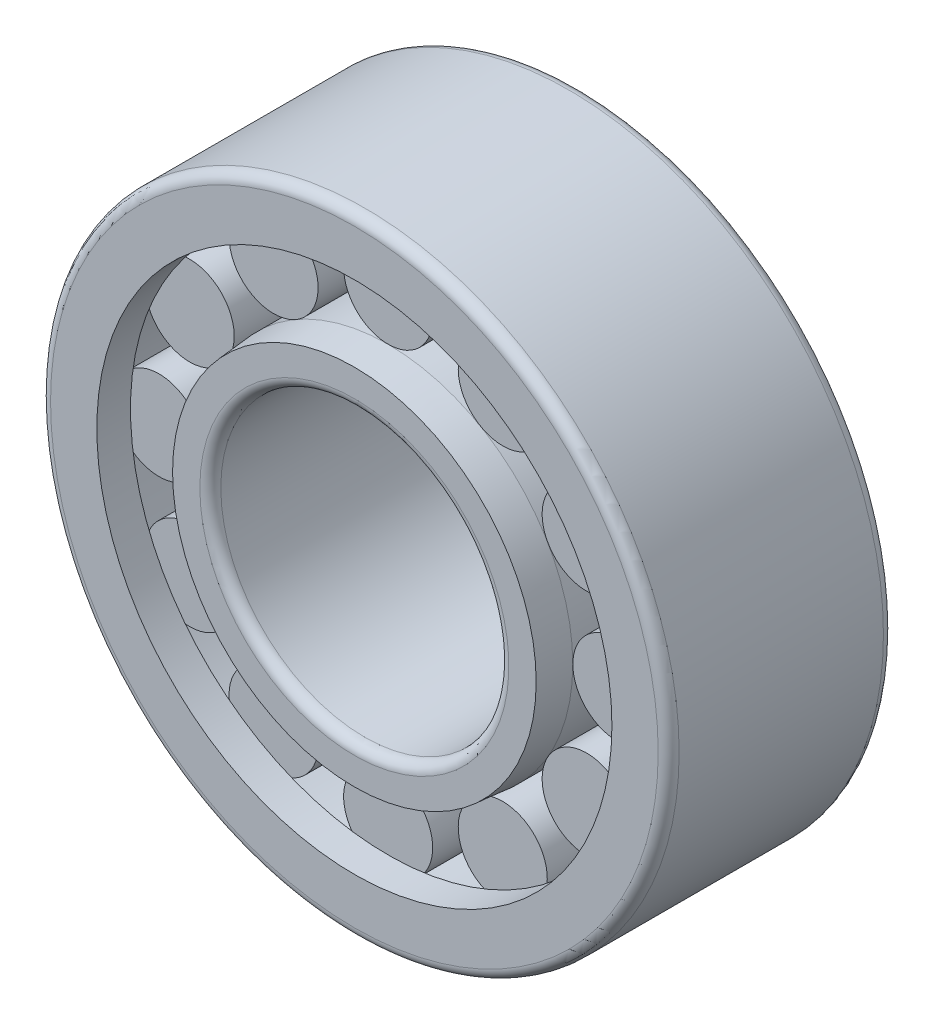
SolidWorks part; units mm, degrees
ref_plane "Front Plane" through (0, 0, 0) normal (0, 0, 1) x (1, 0, 0)
ref_plane "Top Plane" through (0, 0, 0) normal (0, 1, 0) x (1, 0, 0)
ref_plane "Right Plane" through (0, 0, 0) normal (1, 0, 0) x (0, 0, -1)
sketch "BaseSke" plane through (0, 0, 0) normal (1, 0, 0) x (0, 0, -1)
  line L0 (-47.2296, 0) -> (24.6132, 0) construction
  line L1 (-47.2296, 43.75) -> (24.6132, 43.75) construction
  line L2 (0, 129.5214) -> (0, -86.3012) construction
  line L3 (-15.05, 43.75) -> (-15.05, 52.25) construction
  line L4 (-21.5, 60) -> (21.5, 60) construction
  line L5 (-21.5, 27.5) -> (21.5, 27.5) construction
  line L6 (-15.05, 35.25) -> (15.05, 35.25)
  line L7 (-15.05, 35.25) -> (-15.05, 43.75)
  line L8 (-15.05, 43.75) -> (15.05, 43.75)
  line L9 (15.05, 35.25) -> (15.05, 43.75)
  line L10 (-15.05, 52.25) -> (15.05, 52.25) construction
  line L11 (15.05, 52.25) -> (15.05, 43.75) construction
  dimension "D2" = 30.1
  dimension "D1" = 87.5
revolve "Roller" add sketch "BaseSke" angle 360 about L8
sketch "OuterRaceSke" plane through (0, 0, 0) normal (1, 0, 0) x (0, 0, -1)
  line L0 (0, 0) -> (0, 87.5396) construction
  line L1 (-21.5, 60) -> (21.5, 60)
  line L2 (-21.5, 60) -> (-21.5, 49.1667)
  line L3 (-21.5, 49.1667) -> (-15.075, 49.1667)
  line L4 (21.5, 60) -> (21.5, 49.1667)
  line L5 (-50.3916, 0) -> (55.2197, 0) construction
  line L6 (-15.05, 52.25) -> (15.05, 52.25) construction
  line L7 (15.075, 49.1667) -> (21.5, 49.1667)
  line L9 (-15.075, 49.1667) -> (-15.075, 52.23)
  line L10 (-15.075, 52.23) -> (15.075, 52.23)
  line L11 (15.075, 49.1667) -> (15.075, 52.23)
  dimension "D2" = 98.3333
  dimension "D1" = 30.15
  dimension "D3" = 0.02
revolve "OuterRace" add sketch "OuterRaceSke" angle 360 about L5
sketch "InnerRaceSke" plane through (0, 0, 0) normal (1, 0, 0) x (0, 0, -1)
  line L0 (-70.8626, 0) -> (113.5527, 0) construction
  line L1 (0, 58.441) -> (0, -70.8113) construction
  line L2 (-21.5, 27.5) -> (21.5, 27.5)
  line L3 (-21.5, 27.5) -> (-21.5, 38.3333)
  line L4 (-15.075, 38.3333) -> (-15.075, 35.27)
  line L5 (-15.075, 38.3333) -> (-21.5, 38.3333)
  line L6 (0, 129.5214) -> (0, -86.3012) construction
  line L7 (-15.075, 35.27) -> (15.075, 35.27)
  line L9 (21.5, 27.5) -> (21.5, 38.3333)
  line L10 (15.075, 38.3333) -> (21.5, 38.3333)
  line L11 (15.075, 35.27) -> (15.075, 38.3333)
  line L13 (-15.05, 35.25) -> (15.05, 35.25) construction
  point P17 (0, 27.5)
  dimension "D1" = 30.15
  dimension "D2" = 0.02
  dimension "D3" = 76.6667
revolve "InnerRace" add sketch "InnerRaceSke" angle 360 about L0
fillet "Fillet1" radius 2 4 edges at (27.5, 0, 21.5) (60, 0, -21.5) (60, 0, 21.5) (27.5, 0, -21.5)
sketch "CutGrooveSke" plane through (0, 0, 0) normal (1, 0, 0) x (0, 0, -1)
  line L0 (-51.8407, 0) -> (83.8302, 0) construction
  line L1 (-10.75, -78.8) -> (-12.9, -78.8)
  line L2 (-10.75, -78.8) -> (-10.75, -58.8)
  line L3 (-10.75, -58.8) -> (-12.9, -58.8)
  line L4 (-12.9, -78.8) -> (-12.9, -58.8)
  dimension "D1" = 58.8
  dimension "D3" = 2.15
  dimension "D4" = 20
  dimension "D2" = 10.75
revolve "CutGroove" [suppressed] cut sketch "CutGrooveSke" angle 360 about L0
sketch "TaperSke" plane through (0, 0, 0) normal (1, 0, 0) x (0, 0, -1)
  line L0 (-21.5, 27.5) -> (21.5, 27.5)
  line L1 (21.5, 27.5) -> (21.5, 31.0833)
  line L2 (21.5, 31.0833) -> (-21.5, 27.5)
  line L7 (-41.2502, 0) -> (40.8606, 0) construction
revolve "Taper" [suppressed] cut sketch "TaperSke" angle 360 about L7
fillet "Fillet2" [suppressed] radius 2
sketch "NFSke" plane through (0, 0, 0) normal (1, 0, 0) x (0, 0, -1)
  line L0 (-54.6114, 0) -> (63.7655, 0) construction
  line L1 (21.5, 52.7921) -> (15.075, 52.23)
  line L2 (15.075, 52.23) -> (15.075, 49.1667)
  line L3 (15.075, 49.1667) -> (21.5, 49.1667)
  line L4 (21.5, 49.1667) -> (21.5, 52.7921)
  dimension "D1" = 5
revolve "NF" [suppressed] cut sketch "NFSke" angle 360 about L0
mirror "N" [suppressed] about plane through (0, 0, 0) normal (0, 0, 1)
sketch "NJSke" plane through (0, 0, 0) normal (1, 0, 0) x (0, 0, -1)
  line L0 (-35.6078, 0) -> (44.429, 0) construction
  line L1 (21.5, 38.3333) -> (15.075, 38.3333)
  line L2 (15.075, 38.3333) -> (15.075, 35.27)
  line L3 (15.075, 35.27) -> (21.5, 34.7079)
  line L4 (21.5, 34.7079) -> (21.5, 38.3333)
  dimension "D1" = 5
revolve "NJ" cut sketch "NJSke" angle 360 about L0
mirror "NU" about plane through (0, 0, 0) normal (0, 0, 1) of "NJ"
pattern_circular "CirPatternBall" count 12 over 360 about axis through (0, 0, 50.3916) along (0, 0, -1) of "Roller"
sketch "SimplifiedSke" plane through (0, 0, 0) normal (1, 0, 0) x (0, 0, -1)
  line L0 (37.5911, 0) -> (-37.5911, 0) construction
  line L1 (-13.1351, 43.75) -> (13.151, 43.75) construction
  line L2 (-15.05, 52.25) -> (15.05, 52.25)
  line L3 (-15.05, 52.25) -> (-15.05, 35.25)
  line L4 (-15.05, 35.25) -> (15.05, 35.25)
  line L5 (15.05, 52.25) -> (15.05, 35.25)
  line L6 (-47.2296, 43.75) -> (24.6132, 43.75) construction
revolve "Simplified" [suppressed] add sketch "SimplifiedSke" angle 360 about L0
equation "\"D2@BaseSke\" = \"Bearing_Thickness@BaseSke\"*0.7"
equation "\"D1@BaseSke\" =  ( \"Bearing_Outside_Diameter@BaseSke\" + \"Bearing_Inside_Diameter@BaseSke\" )  / 2"
equation "\"D1@OuterRaceSke\" = \"Bearing_Thickness@BaseSke\"*0.7+0.05"
equation "\"D2@OuterRaceSke\" =\"Bearing_Outside_Diameter@BaseSke\" -  ( \"Bearing_Outside_Diameter@BaseSke\" - \"Bearing_Inside_Diameter@BaseSke\"  )/ 3 "
equation "\"D1@InnerRaceSke\" = \"Bearing_Thickness@BaseSke\"*0.7+0.05"
equation "\"D3@InnerRaceSke\" = \"Bearing_Inside_Diameter@BaseSke\" +  ( \"Bearing_Outside_Diameter@BaseSke\" - \"Bearing_Inside_Diameter@BaseSke\" ) / 3 "
equation "\"D1@CirPatternBall\" =  int(  ( \"Bearing_Outside_Diameter@BaseSke\" + \"Bearing_Inside_Diameter@BaseSke\" )  / 2 *  pi  /  ( \"Bearing_Outside_Diameter@BaseSke\" - \"Bearing_Inside_Diameter@BaseSke\" ) * 3 ) "
equation "\"D1@CutGrooveSke\" = \"Bearing_Outside_Diameter@BaseSke\" * 0.49"
equation "\"D2@CutGrooveSke\" = \"Bearing_Thickness@BaseSke\" *0.25"
equation "\"D3@CutGrooveSke\" = \"Bearing_Thickness@BaseSke\"/20"
equation "\"Taper@TaperSke\" = \"Bearing_Thickness@BaseSke\"/12"
equation "\"D1@Fillet2\" = \"Fillet_radius@Fillet1\""
